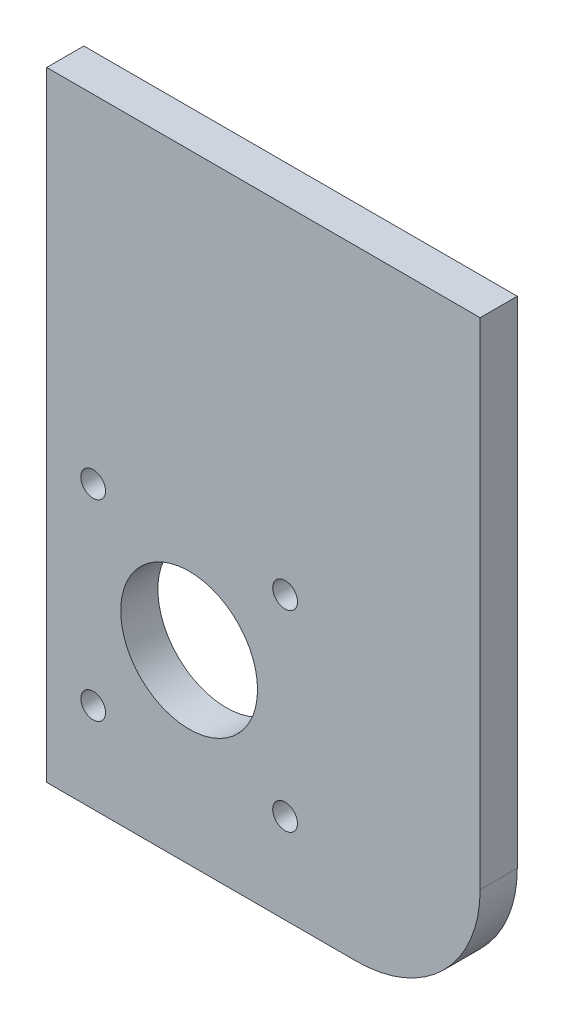
SolidWorks part; units mm, degrees
material "Клен"
ref_plane "Спереди" through (0, 0, 0) normal (0, 0, 1) x (1, 0, 0)
ref_plane "Сверху" through (0, 0, 0) normal (0, 1, 0) x (1, 0, 0)
ref_plane "Справа" through (0, 0, 0) normal (1, 0, 0) x (0, 0, -1)
sketch "Эскиз1" plane through (0, 0, 0) normal (0, 0, 1) x (1, 0, 0)
  line L0 (6, -293.8462) -> (6, -393.8462)
  line L1 (6, -293.8462) -> (6, -593.8462) construction
  line L7 (6, -293.8462) -> (76, -293.8462)
  line L12 (76, -293.8462) -> (76, -373.8462)
  line L14 (56, -393.8462) -> (6, -393.8462)
  arc A0 (76, -373.8462) -> (56, -393.8462) centre (56, -373.8462) cw
  dimension "D2" = 20
  dimension "D1" = 100
extrude "Бобышка-Вытянуть1" add sketch "Эскиз1" against normal blind 6 contours L0 L14 A0 L12 L7
sketch "Эскиз2" plane through (0, 0, 0) normal (0, 0, 1) x (1, 0, 0)
  line L2 (29, -363.8462) -> (29, -412.3555) construction
  line L3 (29, -363.8462) -> (44.8419, -363.8462) construction
  line L4 (76, -293.8462) -> (76, -373.8462) construction
  line L5 (6, -293.8462) -> (76, -293.8462) construction
  circle A0 centre (29, -363.8462) radius 11.05
  circle A1 centre (44.5, -379.3462) radius 2
  circle A2 centre (13.5, -379.3462) radius 2
  circle A3 centre (13.5, -348.3462) radius 2
  circle A4 centre (44.5, -348.3462) radius 2
  dimension "D2" = 22.1
  dimension "D3" = 4
  dimension "D1" = 70
  dimension "D4" = 15.5
  dimension "D5" = 15.5
  dimension "D6" = 47
extrude "Вырез-Вытянуть1" cut sketch "Эскиз2" against normal through all
